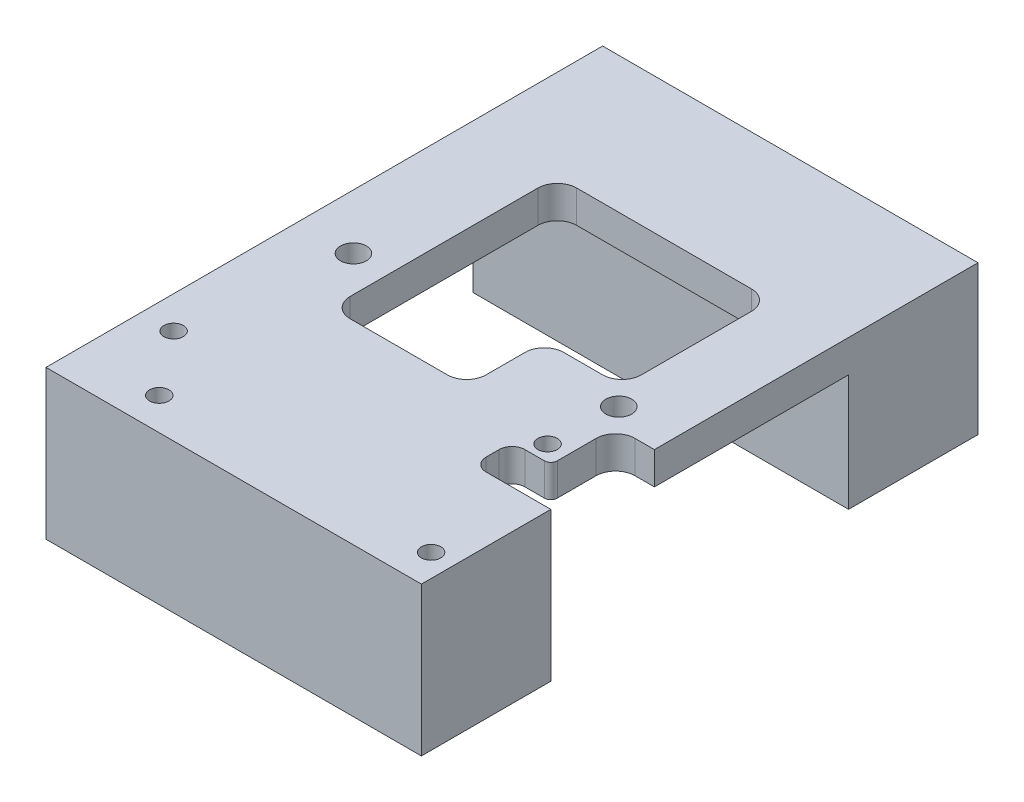
SolidWorks part; units mm, degrees
ref_plane "Front Plane" through (0, 0, 0) normal (0, 0, 1) x (1, 0, 0)
ref_plane "Top Plane" through (0, 0, 0) normal (0, 1, 0) x (1, 0, 0)
ref_plane "Right Plane" through (0, 0, 0) normal (1, 0, 0) x (0, 0, -1)
sketch "Sketch1" plane through (0, 0, 0) normal (0, 1, 0) x (1, 0, 0)
  line L0 (29, 0) -> (-29, 0) construction
  line L1 (0, -43) -> (0, 43) construction
  line L2 (-29, -43) -> (-29, 43)
  line L3 (-29, 43) -> (29, 43)
  line L4 (29, 43) -> (29, -43)
  line L5 (-29, -43) -> (29, -43)
  point P4 (0, 0)
  point P8 (0, 0)
  dimension "D1" = 58
  dimension "D2" = 43
extrude "Boss-Extrude1" add sketch "Sketch1" along normal blind 23
sketch "Sketch2" plane through (0, 0, 0) normal (0, 1, 0) x (1, 0, 0)
  line L0 (29, -43) -> (29, -23) construction
  line L1 (29, -43) -> (29, 43) construction
  line L2 (29, -23) -> (17, -23)
  line L3 (17, -23) -> (17, -17)
  line L4 (17, -17) -> (23, -17)
  line L5 (23, -17) -> (23, -7)
  line L6 (23, -7) -> (29, -7)
  line L7 (29, -7) -> (29, -23)
  dimension "D1" = 12
  dimension "D2" = 20
  dimension "D3" = 6
  dimension "D4" = 6
  dimension "D5" = 10
extrude "Cut-Extrude1" cut sketch "Sketch2" along normal blind 23
sketch "Sketch3" plane through (0, 0, 0) normal (0, 1, 0) x (1, 0, 0)
  line L0 (-29, -43) -> (-15, -43) construction
  line L1 (-29, -43) -> (29, -43) construction
  line L2 (-15, -43) -> (-15, -13) construction
  line L3 (-15, -13) -> (-15, 22)
  line L4 (-15, 22) -> (18, 22)
  line L5 (-15, -13) -> (6, -13)
  line L6 (18, 22) -> (18, -1)
  line L7 (6, -13) -> (6, -1)
  line L8 (6, -1) -> (18, -1)
  dimension "D1" = 14
  dimension "D2" = 30
  dimension "D3" = 35
  dimension "D4" = 33
  dimension "D5" = 21
  dimension "D6" = 23
extrude "Cut-Extrude2" cut sketch "Sketch3" along normal blind 23
fillet "Fillet1" radius 3 1 edges at (23, 11.5, 7) type face fillet first side face at (23, 11.5, 12) second side face at (26, 11.5, 7)
fillet "Fillet2" radius 2 1 edges at (17, 11.5, 17) type face fillet first side face at (17, 11.5, 20) second side face at (20, 11.5, 17)
fillet "Fillet3" radius 2 1 edges at (17, 11.5, 23) type face fillet first side face at (17, 11.5, 21) second side face at (23, 11.5, 23)
fillet "Fillet4" radius 1 1 edges at (23, 11.5, 17) type face fillet first side face at (21, 11.5, 17) second side face at (23, 11.5, 13.5)
fillet "Fillet5" radius 3 1 edges at (-15, 11.5, 13) type face fillet first side face at (-15, 11.5, -4.5) second side face at (-4.5, 11.5, 13)
fillet "Fillet6" radius 3 1 edges at (6, 11.5, 13) type face fillet first side face at (-3, 11.5, 13) second side face at (6, 11.5, 7)
fillet "Fillet7" radius 3 1 edges at (-15, 11.5, -22) type face fillet first side face at (-15, 11.5, -6) second side face at (1.5, 11.5, -22)
fillet "Fillet8" radius 3 1 edges at (18, 11.5, -22) type face fillet first side face at (3, 11.5, -22) second side face at (18, 11.5, -10.5)
fillet "Fillet9" radius 3 1 edges at (18, 11.5, 1) type face fillet first side face at (18, 11.5, -9) second side face at (12, 11.5, 1)
fillet "Fillet10" radius 3 1 edges at (6, 11.5, 1) type face fillet first side face at (10.5, 11.5, 1) second side face at (6, 11.5, 5.5)
sketch "Sketch4" plane through (0, 0, 0) normal (1, 0, 0) x (0, 0, -1)
  line L0 (-23, 0) -> (-23, 18)
  line L1 (-23, 23) -> (-23, 0) construction
  line L2 (-43, 23) -> (-23, 23) construction
  line L3 (-23, 0) -> (23, 0)
  line L4 (-7, 0) -> (43, 0) construction
  line L5 (23, 0) -> (23, 18)
  line L6 (23, 18) -> (-23, 18)
  dimension "D1" = 5
  dimension "D2" = 20
extrude "Cut-Extrude3" cut sketch "Sketch4" against normal through all both and the other way through all
sketch "Sketch5" plane through (0, 0, 0) normal (0, 1, 0) x (1, 0, 0)
  line L0 (20.5, -43) -> (20.5, -4) construction
  line L1 (-29, -43) -> (29, -43) construction
  line L2 (20.5, -4) -> (-20.5, -4) construction
  line L3 (23, -14.5) -> (20, -14.5) construction
  line L5 (23, -10) -> (23, -16) construction
  line L7 (20, -14.5) -> (20, -43) construction
  line L8 (29, -38) -> (25.5, -38) construction
  line L9 (29, -43) -> (29, -23) construction
  line L10 (25.5, -38) -> (-16.5, -38) construction
  line L11 (-29, -43) -> (-25, -43) construction
  circle A0 centre (20.5, -4) radius 2
  circle A1 centre (-20.5, -4) radius 2
  circle A3 centre (20, -14.5) radius 1.5
  circle A4 centre (-16.5, -38) radius 1.5
  circle A5 centre (25.5, -38) radius 1.5
  circle A7 centre (-24, -28.2854) radius 1.5
  dimension "D2" = 4
  dimension "D5" = 4
  dimension "D7" = 28.5
  dimension "D8" = 3
  dimension "D12" = 3
  dimension "D13" = 3
  dimension "D15" = 3
  dimension "D1" = 8.5
  dimension "D3" = 39
  dimension "D4" = 41
  dimension "D6" = 3
  dimension "D9" = 3.5
  dimension "D10" = 42
  dimension "D11" = 5
  dimension "D14" = 4
extrude "Cut-Extrude4" cut sketch "Sketch5" against normal through all and the other way through all
sketch "Sketch6" plane through (-29, 0, 0) normal (-1, 0, 0) x (0, 0, 1)
  line L0 (43, 23) -> (43, 0) construction
  line L1 (23, 0) -> (43, 0) construction
  line L2 (23, 18) -> (23, 0) construction
  circle A0 centre (40, 3) radius 1.5
  circle A1 centre (26, 18) radius 1.5
  dimension "D3" = 3
  dimension "D6" = 3
  dimension "D1" = 3
  dimension "D2" = 3
  dimension "D4" = 3
  dimension "D5" = 18
extrude "Cut-Extrude11" cut sketch "Sketch6" against normal blind 10
sketch "Sketch7" plane through (0, 0, -43) normal (0, 0, -1) x (-1, 0, 0)
  line L0 (-29, 0) -> (29, 0) construction
  line L1 (-29, 23) -> (-29, 0) construction
  line L2 (-29, 23) -> (29, 23) construction
  circle A0 centre (-19.5, 4.5) radius 1.5
  circle A1 centre (-19.5, 18.5) radius 1.5
  dimension "D1" = 3
  dimension "D5" = 3
  dimension "D2" = 4.5
  dimension "D3" = 9.5
  dimension "D4" = 4.5
  dimension "D6" = 9.5
extrude "Cut-Extrude12" cut sketch "Sketch7" against normal blind 10
